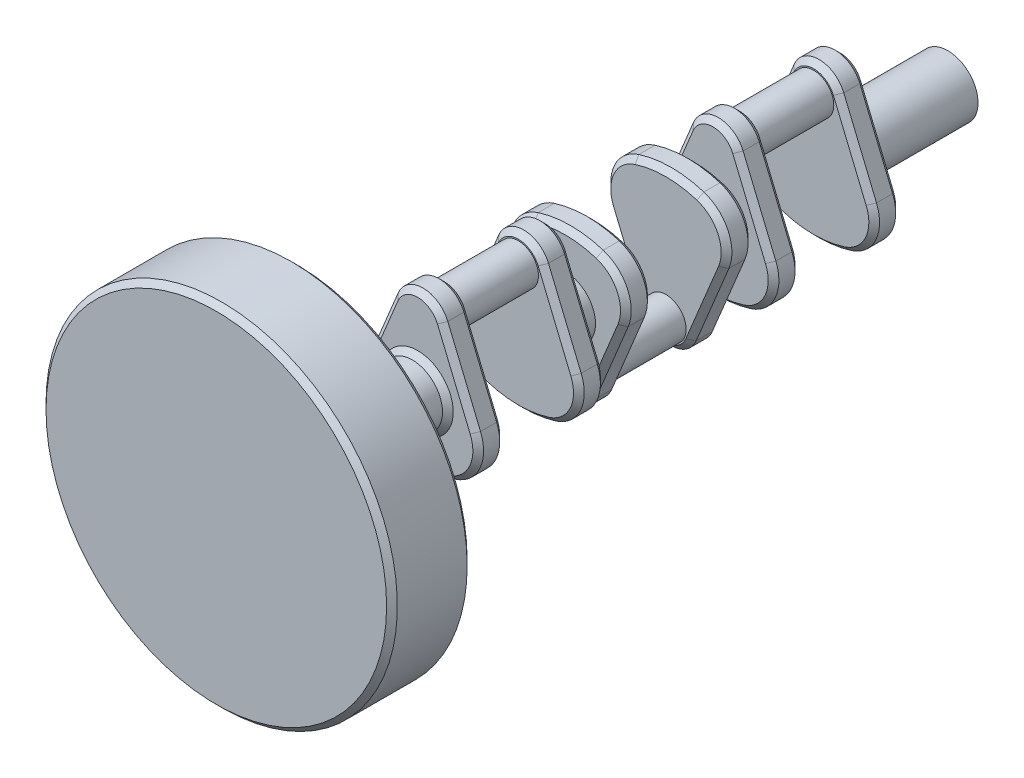
SolidWorks part; units mm, degrees
note: '?' marks a value the reader was unsure of.
material "6061-T6 (SS)"
ref_plane "Front" through (0, 0, 0) normal (0, 0, 1) x (1, 0, 0)
ref_plane "Top" through (0, 0, 0) normal (0, 1, 0) x (1, 0, 0)
ref_plane "Right" through (0, 0, 0) normal (1, 0, 0) x (0, 0, -1)
other "Center of Mass"
sketch "Sketch1" plane through (0, 0, 0) normal (0, 0, 1) x (1, 0, 0)
  circle A1 centre (0, 0) radius 9.525
  dimension "D2" = 19.05
extrude "Boss-Extrude1" add sketch "Sketch1" against normal blind 34.925 contours A1
sketch "Sketch2" plane through (0, 0, -34.925) normal (0, 0, -1) x (-1, 0, 0)
  line L0 (-11.7333, 4.8601) -> (-33.5074, -47.7074)
  line L1 (11.7333, 4.8601) -> (33.5074, -47.7074)
  line L2 (0, 0) -> (0, 30.2986) construction
  arc A0 (11.7333, 4.8601) -> (-11.7333, 4.8601) centre (0, 0) ccw
  arc A1 (-33.5074, -47.7074) -> (33.5074, -47.7074) centre (0, -9.525) ccw
  point P8 (-17.7192, 4.6361)
  point P9 (37.835, -44.8)
  point P11 (32.0961, -43.1879)
  point P13 (12.6403, 1.2299)
  point P14 (12.5018, 2.2349)
  point P15 (0, 0)
  point P16 (0, 0)
  dimension "D1" = 12.7
  dimension "D2" = 50.8
  dimension "D3" = 45
  dimension "D4" = 9.525
extrude "Boss-Extrude2" add sketch "Sketch2" along normal blind 12.7
fillet "Fillet1" radius 19.05 2 edges at (33.5074, -47.7074, -41.275) (-33.5074, -47.7074, -41.275)
ref_plane "Plane1" through (0, 0, -17.4625) normal (0, 0, 1) x (1, 0, 0)
mirror "Mirror2" about plane through (0, 0, -17.4625) normal (0, 0, 1) of bodies 102
ref_point "Point1"
sketch "Sketch3" plane through (0, 0, -47.625) normal (0, 0, -1) x (-1, 0, 0)
  circle A0 centre (0, -28.4865) radius 14.2875
  point P0 (0, -28.4865)
  dimension "D1" = 28.575
extrude "Boss-Extrude3" add sketch "Sketch3" along normal blind 9.525 separate body
pattern_linear "LPattern1" count 3 spacing 69.85 along (0, 0, -1) of bodies 104
ref_axis "Axis1" through (0, -28.4865, -57.15) along (0, 0, 1)?
move or copy body "Body-Move/Copy1" bodies to move or copy 106 copy no rotation origin (0, -28.4865, 0) rotation axis (0, 0, 1) rotation angle 180
pattern_linear "LPattern2" count 2 spacing 69.85 along (0, 0, -1) of "Boss-Extrude3"
sketch "Sketch4" plane through (0, 0, 12.7) normal (0, 0, 1) x (1, 0, 0)
  circle A0 centre (0, -28.4865) radius 14.2875 construction
  circle A1 centre (0, -28.4865) radius 14.2875
extrude "Boss-Extrude4" add sketch "Sketch4" along normal blind 57.15
sketch "Sketch5" plane through (0, 0, -187.325) normal (0, 0, -1) x (-1, 0, 0)
  line L2 (-11.7333, 4.8601) -> (-27.2069, -32.4965)
  line L3 (27.2069, -32.4965) -> (11.7333, 4.8601)
  line L4 (-11.7333, 4.8601) -> (-27.2069, -32.4965)
  line L5 (27.2069, -32.4965) -> (11.7333, 4.8601)
  circle A0 centre (0, -28.4865) radius 14.2875 construction
  circle A1 centre (0, -28.4865) radius 14.2875
  arc A4 (-27.2069, -32.4965) -> (-15.3712, -57.9437) centre (-9.607, -39.7867) ccw
  arc A5 (-15.3712, -57.9437) -> (15.3712, -57.9437) centre (0, -9.525) ccw
  arc A6 (15.3712, -57.9437) -> (27.2069, -32.4965) centre (9.607, -39.7867) ccw
  arc A7 (11.7333, 4.8601) -> (-11.7333, 4.8601) centre (0, 0) ccw
  arc A8 (-27.2069, -32.4965) -> (-15.3712, -57.9437) centre (-9.607, -39.7867) ccw
  arc A9 (-15.3712, -57.9437) -> (15.3712, -57.9437) centre (0, -9.525) ccw
  arc A10 (15.3712, -57.9437) -> (27.2069, -32.4965) centre (9.607, -39.7867) ccw
  arc A11 (11.7333, 4.8601) -> (-11.7333, 4.8601) centre (0, 0) ccw
  dimension "D1" = 0
extrude "Boss-Extrude5" add sketch "Sketch5" along normal blind 50.8 contours A1
sketch "Sketch6" plane through (0, 0, 69.85) normal (0, 0, 1) x (1, 0, 0)
  circle A0 centre (0, -28.4865) radius 83.1071
extrude "Boss-Extrude6" add sketch "Sketch6" along normal blind 38.1
combine bodies "Combine1" operation type add bodies to combine 105 108 109 111 112
chamfer "Chamfer1" distance 2.54 angle 45 77 edges at (-14.2875, -28.4865, -187.325) (14.2875, -28.4865, 12.7) (14.2875, -28.4865, 69.85) (-26.8801, -47.8205, -174.625) (-19.4701, -13.8182, -174.625) (0, -60.325, -174.625) (0, 12.7, -174.625) (26.8801, -47.8205, -174.625) (19.4701, -13.8182, -174.625) (-26.8801, -47.8205, -187.325) (-19.4701, -13.8182, -187.325) (0, -60.325, -187.325) (0, 12.7, -187.325) (26.8801, -47.8205, -187.325) (19.4701, -13.8182, -187.325) (-26.8801, -47.8205, -139.7) (-19.4701, -13.8182, -139.7) (0, -60.325, -139.7) (0, 12.7, -139.7) (26.8801, -47.8205, -139.7) (19.4701, -13.8182, -139.7) (-26.8801, -47.8205, -127) (-19.4701, -13.8182, -127) (0, -60.325, -127) (0, 12.7, -127) (26.8801, -47.8205, -127) (19.4701, -13.8182, -127) (-19.4701, -43.1547, -117.475) (-26.8801, -9.1524, -117.475) (0, -69.6729, -117.475) (0, 3.3521, -117.475) (19.4701, -43.1547, -117.475) (26.8801, -9.1524, -117.475) (-19.4701, -43.1547, -104.775) (0, -69.6729, -104.775) (-26.8801, -9.1524, -104.775) (19.4701, -43.1547, -104.775) (0, 3.3521, -104.775) (26.8801, -9.1524, -104.775) (-19.4701, -43.1547, -69.85) (0, -69.6729, -69.85) (-26.8801, -9.1524, -69.85) (19.4701, -43.1547, -69.85) (0, 3.3521, -69.85) (26.8801, -9.1524, -69.85) (-19.4701, -43.1547, -57.15) (-26.8801, -9.1524, -57.15) (0, -69.6729, -57.15) (0, 3.3521, -57.15) (19.4701, -43.1547, -57.15) (26.8801, -9.1524, -57.15) (-19.4701, -13.8182, -47.625) (0, 12.7, -47.625) (-26.8801, -47.8205, -47.625) (19.4701, -13.8182, -47.625) (0, -60.325, -47.625) (26.8801, -47.8205, -47.625) (-19.4701, -13.8182, -34.925) (-26.8801, -47.8205, -34.925) (0, 12.7, -34.925) (0, -60.325, -34.925) (19.4701, -13.8182, -34.925) (26.8801, -47.8205, -34.925) (-19.4701, -13.8182, 0) (-26.8801, -47.8205, 0) (0, 12.7, 0) (0, -60.325, 0) (19.4701, -13.8182, 0) (26.8801, -47.8205, 0) (-19.4701, -13.8182, 12.7) (0, 12.7, 12.7) (-26.8801, -47.8205, 12.7) (19.4701, -13.8182, 12.7) (0, -60.325, 12.7) (26.8801, -47.8205, 12.7) (83.1071, -28.4865, 69.85) (83.1071, -28.4865, 107.95)
